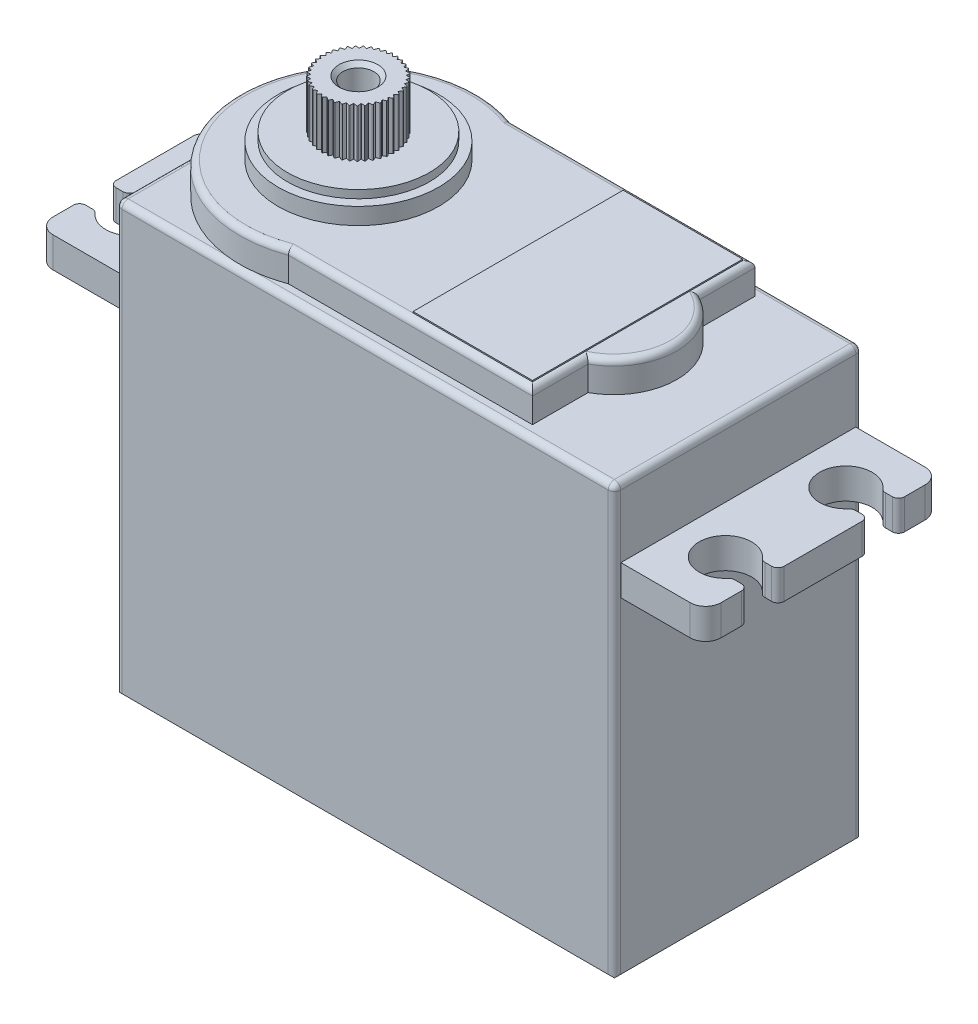
SolidWorks part; units mm, degrees
ref_plane "Front Plane" through (0, 0, 0) normal (0, 0, 1) x (1, 0, 0)
ref_plane "Top Plane" through (0, 0, 0) normal (0, 1, 0) x (1, 0, 0)
ref_plane "Right Plane" through (0, 0, 0) normal (1, 0, 0) x (0, 0, -1)
sketch "Sketch1" plane through (0, 0, 10) normal (0, 1, 0) x (1, 0, 0)
  line L0 (-20.1676, 20.0203) -> (-20.1676, -0.0203)
  line L1 (-20.1676, -0.0203) -> (20.1676, -0.0203)
  line L2 (20.1676, -0.0203) -> (20.1676, 20.0203)
  line L3 (20.1676, 20.0203) -> (-20.1676, 20.0203)
  line L4 (-20.1676, 20.0203) -> (20.1676, -0.0203) construction
  line L5 (20.1676, 20.0203) -> (-20.1676, -0.0203) construction
  point P5 (0, 10)
  dimension "D1" = 20.0406
  dimension "D2" = 40.3352
extrude "Boss-Extrude1" add sketch "Sketch1" against normal mid plane 36.9316
sketch "Sketch2" plane through (0, 18.4658, 8.65) normal (0, -1, 0) x (-1, 0, 0)
  line L0 (-12.5182, -0.35) -> (-12.5182, 17.65)
  line L1 (-12.5182, 17.65) -> (7.2213, 17.65)
  line L2 (7.2213, -0.35) -> (-12.5182, -0.35)
  line L3 (20.1676, 8.65) -> (-20.1676, 8.65) construction
  line L4 (20.1676, 18.6703) -> (20.1676, -1.3703) construction
  line L5 (-20.1676, -1.3703) -> (-20.1676, 18.6703) construction
  arc A0 (7.2213, 17.65) -> (7.2213, -0.35) centre (10.5654, 8.65) cw
  point P15 (20.1666, 8.65)
  dimension "D1" = 19.7395
  dimension "D3" = 9.6012
  dimension "D4" = 0.001
  dimension "D2" = 18
extrude "Boss-Extrude2" add sketch "Sketch2" against normal blind 2.5
sketch "Sketch3" plane through (20.1676, 0, 0) normal (1, 0, 0) x (0, 0, -1)
  line L0 (9.5, 12.8778) -> (9.5, 10.414)
  line L1 (9.5, 10.414) -> (-9.5, 10.414)
  line L2 (-9.5, 10.414) -> (-9.5, 12.8778)
  line L3 (-9.5, 12.8778) -> (9.5, 12.8778)
  line L4 (9, 18.4658) -> (-9, 18.4658) construction
  dimension "D1" = 2.4638
  dimension "D2" = 19
  dimension "D3" = 5.588
extrude "Boss-Extrude3" add sketch "Sketch3" along normal blind 6.858
sketch "Sketch4" plane through (0, 10.414, 0) normal (0, -1, 0) x (1, 0, 0)
  line L0 (27.0256, 3.65) -> (27.0256, 6.1)
  line L1 (27.0256, 6.1) -> (25.737, 6.1)
  line L2 (25.737, 3.65) -> (27.0256, 3.65)
  line L5 (27.0256, 9.5) -> (27.0256, -9.5) construction
  arc A0 (25.737, 6.1) -> (25.737, 3.65) centre (24.0006, 4.875) ccw
  dimension "D3" = 2.125
  dimension "D1" = 1.2886
  dimension "D2" = 2.45
extrude "Cut-Extrude1" cut sketch "Sketch4" against normal through all
sketch "Sketch5" plane through (0, 10.414, 0) normal (0, -1, 0) x (1, 0, 0)
  line L0 (27.0256, -6.1) -> (27.0256, -3.65)
  line L1 (27.0256, -3.65) -> (25.737, -3.65)
  line L2 (25.737, -6.1) -> (27.0256, -6.1)
  line L3 (27.0256, 3.65) -> (27.0256, -9.5) construction
  arc A0 (25.737, -3.65) -> (25.737, -6.1) centre (24.0006, -4.875) ccw
  dimension "D3" = 2.125
  dimension "D1" = 1.2886
  dimension "D2" = 2.45
extrude "Cut-Extrude2" cut sketch "Sketch5" against normal through all
sketch "Sketch6" plane through (-20.1676, 0, 0) normal (-1, 0, 0) x (0, 0, 1)
  line L0 (-9.5, 10.414) -> (-9.5, 12.8778)
  line L1 (-9.5, 12.8778) -> (9.5, 12.8778)
  line L2 (9.5, 12.8778) -> (9.5, 10.414)
  line L3 (9.5, 10.414) -> (-9.5, 10.414)
  line L4 (-10.0203, 18.4658) -> (10.0203, 18.4658) construction
  dimension "D1" = 2.4638
  dimension "D2" = 19
  dimension "D3" = 5.588
extrude "Boss-Extrude4" add sketch "Sketch6" along normal blind 6.858
sketch "Sketch7" plane through (0, 10.414, 0) normal (0, -1, 0) x (1, 0, 0)
  line L0 (-27.0256, -6.1) -> (-25.737, -6.1)
  line L1 (-25.737, -3.65) -> (-27.0256, -3.65)
  line L2 (-27.0256, -3.65) -> (-27.0256, -6.1)
  line L3 (-27.0256, -9.5) -> (-27.0256, 9.5) construction
  arc A0 (-25.737, -6.1) -> (-25.737, -3.65) centre (-24.0006, -4.875) ccw
  dimension "D3" = 2.125
  dimension "D1" = 1.2886
  dimension "D2" = 2.45
extrude "Cut-Extrude3" cut sketch "Sketch7" against normal through all
sketch "Sketch8" plane through (0, 10.414, 0) normal (0, -1, 0) x (1, 0, 0)
  line L0 (-27.0256, 3.65) -> (-25.737, 3.65)
  line L1 (-25.737, 6.1) -> (-27.0256, 6.1)
  line L2 (-27.0256, 6.1) -> (-27.0256, 3.65)
  line L3 (-27.0256, -3.65) -> (-27.0256, 9.5) construction
  arc A0 (-25.737, 3.65) -> (-25.737, 6.1) centre (-24.0006, 4.875) ccw
  dimension "D2" = 2.125
  dimension "D1" = 1.2886
  dimension "D3" = 2.45
extrude "Cut-Extrude4" cut sketch "Sketch8" against normal through all
sketch "Sketch9" plane through (0, 18.4658, 8.65) normal (0, -1, 0) x (-1, 0, 0)
  line L0 (-12.5182, 13.15) -> (-12.5182, 4.15)
  line L3 (-12.5182, 17.65) -> (-12.5182, -0.35) construction
  arc A0 (-12.5182, 4.15) -> (-12.5182, 13.15) centre (-10.082, 8.65) cw
  point P3 (-12.5182, 8.65)
  dimension "D1" = 5.1171
  dimension "D2" = 9
extrude "Boss-Extrude5" add sketch "Sketch9" against normal blind 2.5
sketch "Sketch10" plane through (0, 20.9658, 0) normal (0, 1, 0) x (-1, 0, 0)
  circle A0 centre (10.5654, 0) radius 6.5
  dimension "D1" = 13
extrude "Boss-Extrude6" add sketch "Sketch10" along normal blind 1.35
sketch "Sketch11" plane through (0, 22.3158, 0) normal (0, 1, 0) x (-1, 0, 0)
  circle A0 centre (10.5654, 0) radius 5.75
extrude "Boss-Extrude7" add sketch "Sketch11" along normal blind 0.65
sketch "Sketch12" plane through (0, 22.9658, 0) normal (0, 1, 0) x (-1, 0, 0)
  line B0 (9.3322, -2.458) -> (9.0287, -2.5765)
  line B1 (9.0287, -2.5765) -> (8.9887, -2.2531)
  line B2 (8.9715, -2.241) -> (8.6534, -2.3117)
  line B3 (8.6534, -2.3117) -> (8.6632, -1.986)
  line B4 (8.6481, -1.9714) -> (8.3229, -1.9928)
  line B5 (8.3229, -1.9928) -> (8.3824, -1.6724)
  line B6 (8.3696, -1.6556) -> (8.045, -1.6271)
  line B7 (8.045, -1.6271) -> (8.1527, -1.3195)
  line B8 (8.1426, -1.301) -> (7.8261, -1.2233)
  line B9 (7.8261, -1.2233) -> (7.9795, -0.9358)
  line B10 (7.9724, -0.9159) -> (7.6715, -0.7908)
  line B11 (7.6715, -0.7908) -> (7.867, -0.5301)
  line B12 (7.863, -0.5094) -> (7.5847, -0.3398)
  line B13 (7.5847, -0.3398) -> (7.8177, -0.112)
  line B14 (7.8169, -0.0909) -> (7.5678, 0.1192)
  line B15 (7.5678, 0.1192) -> (7.8328, 0.3088)
  line B16 (7.8352, 0.3297) -> (7.6211, 0.5754)
  line B17 (7.6211, 0.5754) -> (7.912, 0.7223)
  line B18 (7.9176, 0.7426) -> (7.7434, 1.0181)
  line B19 (7.7434, 1.0181) -> (8.0533, 1.1189)
  line B20 (8.062, 1.1381) -> (7.9319, 1.4369)
  line B21 (7.9319, 1.4369) -> (8.2536, 1.4892)
  line B22 (8.265, 1.5069) -> (8.1821, 1.8221)
  line B23 (8.1821, 1.8221) -> (8.508, 1.8247)
  line B24 (8.522, 1.8404) -> (8.4882, 2.1645)
  line B25 (8.4882, 2.1645) -> (8.8106, 2.1174)
  line B26 (8.8269, 2.1308) -> (8.8429, 2.4562)
  line B27 (8.8429, 2.4562) -> (9.1544, 2.3604)
  line B28 (9.1725, 2.3712) -> (9.2381, 2.6904)
  line B29 (9.2381, 2.6904) -> (9.5313, 2.5481)
  line B30 (9.5508, 2.556) -> (9.6643, 2.8615)
  line B31 (9.6643, 2.8615) -> (9.9324, 2.6761)
  line B32 (9.9529, 2.6809) -> (10.1117, 2.9655)
  line B33 (10.1117, 2.9655) -> (10.3483, 2.7414)
  line B34 (10.3693, 2.743) -> (10.5697, 3)
  line B35 (10.5697, 3) -> (10.7693, 2.7424)
  line B36 (10.7903, 2.7408) -> (11.0276, 2.9642)
  line B37 (11.0276, 2.9642) -> (11.1855, 2.6792)
  line B38 (11.2061, 2.6743) -> (11.4746, 2.8589)
  line B39 (11.4746, 2.8589) -> (11.5873, 2.5531)
  line B40 (11.6068, 2.5452) -> (11.9004, 2.6866)
  line B41 (11.9004, 2.6866) -> (11.965, 2.3672)
  line B42 (11.9831, 2.3564) -> (12.2948, 2.4513)
  line B43 (12.2948, 2.4513) -> (12.31, 2.1258)
  line B44 (12.3262, 2.1124) -> (12.6488, 2.1586)
  line B45 (12.6488, 2.1586) -> (12.614, 1.8346)
  line B46 (12.628, 1.8188) -> (12.9539, 1.8153)
  line B47 (12.9539, 1.8153) -> (12.87, 1.5004)
  line B48 (12.8815, 1.4827) -> (13.203, 1.4294)
  line B49 (13.203, 1.4294) -> (13.0721, 1.131)
  line B50 (13.0807, 1.1117) -> (13.3903, 1.01)
  line B51 (13.3903, 1.01) -> (13.2153, 0.7351)
  line B52 (13.2209, 0.7147) -> (13.5113, 0.567)
  line B53 (13.5113, 0.567) -> (13.2965, 0.322)
  line B54 (13.2989, 0.301) -> (13.5634, 0.1106)
  line B55 (13.5634, 0.1106) -> (13.3136, -0.0987)
  line B56 (13.3128, -0.1198) -> (13.5451, -0.3483)
  line B57 (13.5451, -0.3483) -> (13.2664, -0.5171)
  line B58 (13.2623, -0.5378) -> (13.457, -0.7991)
  line B59 (13.457, -0.7991) -> (13.1558, -0.9233)
  line B60 (13.1486, -0.9431) -> (13.3012, -1.2311)
  line B61 (13.3012, -1.2311) -> (12.9845, -1.3079)
  line B62 (12.9744, -1.3264) -> (13.0812, -1.6343)
  line B63 (13.0812, -1.6343) -> (12.7565, -1.6618)
  line B64 (12.7437, -1.6786) -> (12.8022, -1.9992)
  line B65 (12.8022, -1.9992) -> (12.4771, -1.9768)
  line B66 (12.4619, -1.9914) -> (12.4708, -2.3172)
  line B67 (12.4708, -2.3172) -> (12.1529, -2.2455)
  line B68 (12.1357, -2.2576) -> (12.0948, -2.5809)
  line B69 (12.0948, -2.5809) -> (11.7916, -2.4615)
  line B70 (11.7727, -2.4708) -> (11.6829, -2.7841)
  line B71 (11.6829, -2.7841) -> (11.4014, -2.6198)
  line B72 (11.3813, -2.6262) -> (11.2448, -2.9221)
  line B73 (11.2448, -2.9221) -> (10.9917, -2.7168)
  line B74 (10.9709, -2.7199) -> (10.7908, -2.9915)
  line B75 (10.7908, -2.9915) -> (10.572, -2.75)
  line B76 (10.5509, -2.75) -> (10.3315, -2.9909)
  line B77 (10.3315, -2.9909) -> (10.1522, -2.7188)
  line B78 (10.1313, -2.7155) -> (9.8777, -2.9201)
  line B79 (9.8777, -2.9201) -> (9.742, -2.6238)
  line B80 (9.7219, -2.6174) -> (9.44, -2.7809)
  line B81 (9.44, -2.7809) -> (9.3511, -2.4674)
  arc B82 (9.3511, -2.4674) -> (9.3322, -2.458) centre (10.5654, 0) cw
  arc B83 (8.9887, -2.2531) -> (8.9715, -2.241) centre (10.5654, 0) cw
  arc B84 (8.6632, -1.986) -> (8.6481, -1.9714) centre (10.5654, 0) cw
  arc B85 (8.3824, -1.6724) -> (8.3696, -1.6556) centre (10.5654, 0) cw
  arc B86 (8.1527, -1.3195) -> (8.1426, -1.301) centre (10.5654, 0) cw
  arc B87 (7.9795, -0.9358) -> (7.9724, -0.9159) centre (10.5654, 0) cw
  arc B88 (7.867, -0.5301) -> (7.863, -0.5094) centre (10.5654, 0) cw
  arc B89 (7.8177, -0.112) -> (7.8169, -0.0909) centre (10.5654, 0) cw
  arc B90 (7.8328, 0.3088) -> (7.8352, 0.3297) centre (10.5654, 0) cw
  arc B91 (7.912, 0.7223) -> (7.9176, 0.7426) centre (10.5654, 0) cw
  arc B92 (8.0533, 1.1189) -> (8.062, 1.1381) centre (10.5654, 0) cw
  arc B93 (8.2536, 1.4892) -> (8.265, 1.5069) centre (10.5654, 0) cw
  arc B94 (8.508, 1.8247) -> (8.522, 1.8404) centre (10.5654, 0) cw
  arc B95 (8.8106, 2.1174) -> (8.8269, 2.1308) centre (10.5654, 0) cw
  arc B96 (9.1544, 2.3604) -> (9.1725, 2.3712) centre (10.5654, 0) cw
  arc B97 (9.5313, 2.5481) -> (9.5508, 2.556) centre (10.5654, 0) cw
  arc B98 (9.9324, 2.6761) -> (9.9529, 2.6809) centre (10.5654, 0) cw
  arc B99 (10.3483, 2.7414) -> (10.3693, 2.743) centre (10.5654, 0) cw
  arc B100 (10.7693, 2.7424) -> (10.7903, 2.7408) centre (10.5654, 0) cw
  arc B101 (11.1855, 2.6792) -> (11.2061, 2.6743) centre (10.5654, 0) cw
  arc B102 (11.5873, 2.5531) -> (11.6068, 2.5452) centre (10.5654, 0) cw
  arc B103 (11.965, 2.3672) -> (11.9831, 2.3564) centre (10.5654, 0) cw
  arc B104 (12.31, 2.1258) -> (12.3262, 2.1124) centre (10.5654, 0) cw
  arc B105 (12.614, 1.8346) -> (12.628, 1.8188) centre (10.5654, 0) cw
  arc B106 (12.87, 1.5004) -> (12.8815, 1.4827) centre (10.5654, 0) cw
  arc B107 (13.0721, 1.131) -> (13.0807, 1.1117) centre (10.5654, 0) cw
  arc B108 (13.2153, 0.7351) -> (13.2209, 0.7147) centre (10.5654, 0) cw
  arc B109 (13.2965, 0.322) -> (13.2989, 0.301) centre (10.5654, 0) cw
  arc B110 (13.3136, -0.0987) -> (13.3128, -0.1198) centre (10.5654, 0) cw
  arc B111 (13.2664, -0.5171) -> (13.2623, -0.5378) centre (10.5654, 0) cw
  arc B112 (13.1558, -0.9233) -> (13.1486, -0.9431) centre (10.5654, 0) cw
  arc B113 (12.9845, -1.3079) -> (12.9744, -1.3264) centre (10.5654, 0) cw
  arc B114 (12.7565, -1.6618) -> (12.7437, -1.6786) centre (10.5654, 0) cw
  arc B115 (12.4771, -1.9768) -> (12.4619, -1.9914) centre (10.5654, 0) cw
  arc B116 (12.1529, -2.2455) -> (12.1357, -2.2576) centre (10.5654, 0) cw
  arc B117 (11.7916, -2.4615) -> (11.7727, -2.4708) centre (10.5654, 0) cw
  arc B118 (11.4014, -2.6198) -> (11.3813, -2.6262) centre (10.5654, 0) cw
  arc B119 (10.9917, -2.7168) -> (10.9709, -2.7199) centre (10.5654, 0) cw
  arc B120 (10.572, -2.75) -> (10.5509, -2.75) centre (10.5654, 0) cw
  arc B121 (10.1522, -2.7188) -> (10.1313, -2.7155) centre (10.5654, 0) cw
  arc B122 (9.742, -2.6238) -> (9.7219, -2.6174) centre (10.5654, 0) cw
sketch_block_instance "Block1-1"
sketch_block "Block1"
extrude "Boss-Extrude8" add sketch "Sketch12" along normal blind 3.9
sketch "Sketch13" plane through (-20.1676, 0, 0) normal (-1, 0, 0) x (0, 0, 1)
  line L0 (-3.375, -11.2842) -> (3.375, -11.2842)
  line L1 (3.375, -11.2842) -> (3.375, -15.2842)
  line L2 (3.375, -15.2842) -> (-3.375, -15.2842)
  line L3 (-3.375, -15.2842) -> (-3.375, -11.2842)
  line L4 (9.6012, 18.4658) -> (-9.6012, 18.4658) construction
  dimension "D1" = 4
  dimension "D2" = 6.75
  dimension "D3" = 29.75
extrude "Boss-Extrude9" add sketch "Sketch13" along normal blind 5 draft 5
ref_plane "Plane2" through (0, 0, 4.875) normal (0, 0, 1) x (1, 0, 0)
ref_plane "Plane3" through (0, 0, -4.875) normal (0, 0, 1) x (1, 0, 0)
hole_wizard "Ø2.5 (2.5) Diameter Hole1" positions "Sketch19" profile "Sketch18" hole size "Ø2.5" standard "ANSI Metric"
sketch "Sketch19" plane through (0, 26.8658, 0) normal (0, 1, 0) x (1, 0, 0)
  point P9 (-10.5654, 0)
sketch "Sketch18" plane through (-10.5654, 26.8658, 0) normal (1, 0, 0) x (0, 0, 1)
  line L0 (0, 0) -> (0, 9.2511)
  line L1 (0, 9.2511) -> (1.25, 8.5)
  line L2 (1.25, 8.5) -> (1.25, 0)
  line L5 (1.25, 0) -> (0, 0)
  line L10 (0, 9.2511) -> (-1.25, 8.5) construction
  line L11 (0, -6.35) -> (0, 107.95) construction
  dimension "Hole Dia." = 2.5
  dimension "Hole Depth" = 8.5
  dimension "Drill Angle" = 118
fillet "Fillet1" radius 0.055 41 edges at (-7.5847, 24.9158, -0.3398) (-11.6829, 24.9158, -2.7841) (-9.8777, 24.9158, -2.9201) (-7.6211, 24.9158, 0.5754) (-12.4708, 24.9158, -2.3172) (-10.7908, 24.9158, -2.9915) (-7.7434, 24.9158, 1.0181) (-7.5678, 24.9158, 0.1192) (-7.6715, 24.9158, -0.7908) (-11.0276, 24.9158, 2.9642) (-12.0948, 24.9158, -2.5809) (-11.4746, 24.9158, 2.8589) (-11.2448, 24.9158, -2.9221) (-10.5697, 24.9158, 3) (-10.3315, 24.9158, -2.9909) (-11.9004, 24.9158, 2.6866) (-10.1117, 24.9158, 2.9655) (-13.5451, 24.9158, -0.3483) (-12.2948, 24.9158, 2.4513) (-13.457, 24.9158, -0.7991) (-9.6643, 24.9158, 2.8615) (-13.3012, 24.9158, -1.2311) (-12.6488, 24.9158, 2.1586) (-13.0812, 24.9158, -1.6343) (-9.2381, 24.9158, 2.6904) (-12.8022, 24.9158, -1.9992) (-12.9539, 24.9158, 1.8153) (-7.8261, 24.9158, -1.2233) (-8.8429, 24.9158, 2.4562) (-8.045, 24.9158, -1.6271) (-13.203, 24.9158, 1.4294) (-8.3229, 24.9158, -1.9928) (-8.4882, 24.9158, 2.1645) (-8.6534, 24.9158, -2.3117) (-13.3903, 24.9158, 1.01) (-9.0287, 24.9158, -2.5765) (-8.1821, 24.9158, 1.8221) (-13.5113, 24.9158, 0.567) (-7.9319, 24.9158, 1.4369) (-9.44, 24.9158, -2.7809) (-13.5634, 24.9158, 0.1106) tangent propagation no
chamfer "Chamfer1" distance 2.5 angle 45 4 edges at (0, -18.4658, 10.0203) (-20.1676, -18.4658, 0) (0, -18.4658, -10.0203) (20.1676, -18.4658, 0)
chamfer "Chamfer2" distance 0.325 angle 45 1 edges at (-10.5654, 26.8658, 1.25)
fillet "Fillet2" radius 0.5 30 edges at (25.737, 11.6459, 3.65) (27.0256, 11.6459, 3.65) (20.1676, 18.4658, 0) (20.1676, 1.25, -10.0203) (0, 18.4658, -10.0203) (-27.0256, 11.6459, -6.1) (25.737, 11.6459, -6.1) (-25.737, 11.6459, -6.1) (-25.737, 11.6459, -3.65) (-20.1676, 18.4658, 0) (-20.1676, 1.25, -10.0203) (-27.0256, 11.6459, -3.65) (-27.0256, 11.6459, 3.65) (-25.737, 11.6459, 3.65) (27.0256, 11.6459, -3.65) (-25.737, 11.6459, 6.1) (-27.0256, 11.6459, 6.1) (15.1991, 20.9658, 0) (12.5182, 20.9658, 6.75) (12.5182, 20.9658, -6.75) (2.6484, 20.9658, 9) (2.6484, 20.9658, -9) (-20.1666, 20.9658, 0) (27.0256, 11.6459, -6.1) (25.737, 11.6459, 6.1) (25.737, 11.6459, -3.65) (27.0256, 11.6459, 6.1) (0, 18.4658, 10.0203) (20.1676, 1.25, 10.0203) (-20.1676, 1.25, 10.0203) tangent propagation no
fillet "Fillet3" radius 1.25 8 edges at (-22.6676, -11.5029, 3.1563) (27.0256, 11.6459, -9.5) (-27.0256, 11.6459, 9.5) (27.0256, 11.6459, 9.5) (-27.0256, 11.6459, -9.5) (-22.6676, -11.5029, -3.1563) (-22.6676, -15.0655, 3.1563) (-22.6676, -15.0655, -3.1563) tangent propagation no
sketch "Sketch20" plane through (0, 20.9658, 0) normal (0, 1, 0) x (1, 0, 0)
  line L0 (-7.3124, -8.5) -> (12.0182, -8.5) construction
  line L1 (12.0182, 8.5) -> (2.3529, 8.5)
  line L2 (12.0182, 8.5) -> (12.0182, -8.5)
  line L3 (12.0182, -8.5) -> (2.3529, -8.5)
  line L4 (2.3529, 8.5) -> (2.3529, -8.5)
extrude "Boss-Extrude10" add sketch "Sketch20" along normal blind 0.1
